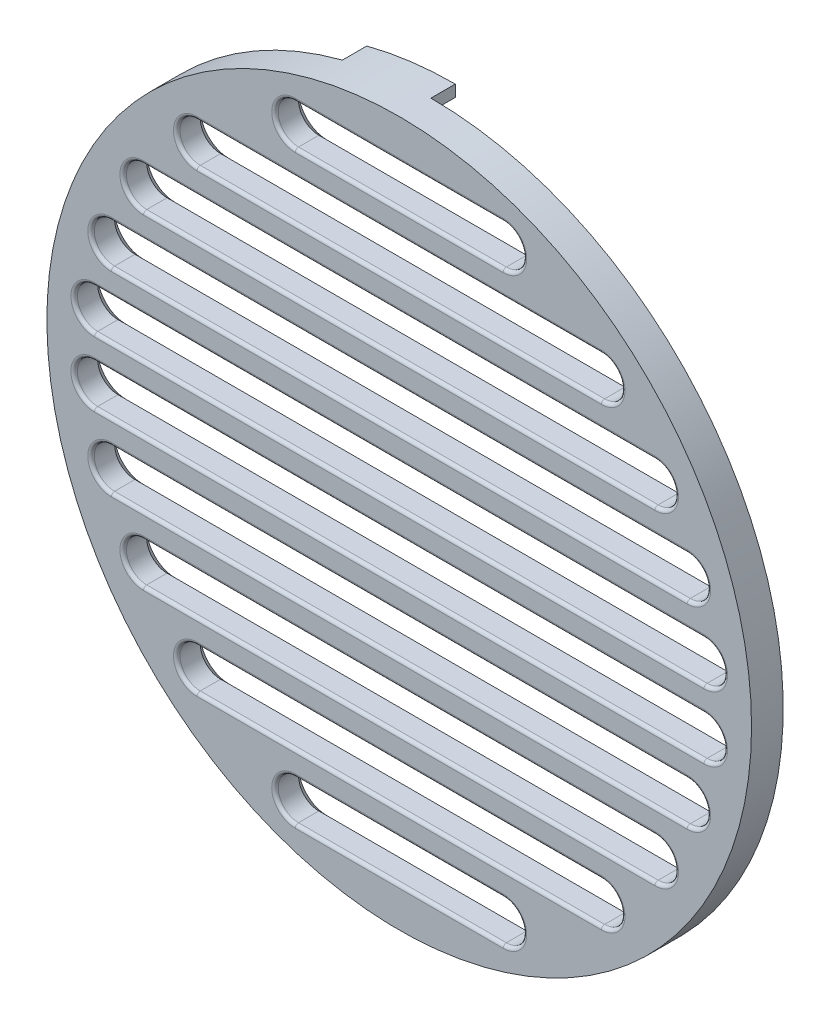
SolidWorks part; units mm, degrees
ref_plane "Alzado" through (0, 0, 0) normal (0, 0, 1) x (1, 0, 0)
ref_plane "Planta" through (0, 0, 0) normal (0, 1, 0) x (1, 0, 0)
ref_plane "Vista lateral" through (0, 0, 0) normal (1, 0, 0) x (0, 0, -1)
sketch "Croquis1" plane through (0, 0, 0) normal (0, 0, 1) x (1, 0, 0)
  line L0 (-6.3927, 18) -> (6.3927, 18) construction
  line L1 (-6.3927, 19.25) -> (6.3927, 19.25)
  line L2 (-6.3927, 16.75) -> (6.3927, 16.75)
  line L3 (0, 0) -> (0, 21) construction
  line L4 (-12.4374, 14) -> (12.4374, 14) construction
  line L5 (-12.4374, 15.25) -> (12.4374, 15.25)
  line L6 (-12.4374, 12.75) -> (12.4374, 12.75)
  line L7 (-15.7324, 10) -> (15.7324, 10) construction
  line L8 (-15.7324, 11.25) -> (15.7324, 11.25)
  line L9 (-15.7324, 8.75) -> (15.7324, 8.75)
  line L10 (-17.7088, 6) -> (17.7088, 6) construction
  line L11 (-17.7088, 7.25) -> (17.7088, 7.25)
  line L12 (-17.7088, 4.75) -> (17.7088, 4.75)
  line L13 (-18.747, 2) -> (18.747, 2) construction
  line L14 (-18.747, 3.25) -> (18.747, 3.25)
  line L15 (-18.747, 0.75) -> (18.747, 0.75)
  line L16 (12.4374, 15.25) -> (14.4374, 15.25) construction
  line L17 (6.3927, 19.25) -> (8.3927, 19.25) construction
  line L18 (15.7324, 11.25) -> (17.7324, 11.25) construction
  line L19 (17.7088, 7.25) -> (19.7088, 7.25) construction
  line L20 (18.747, 3.25) -> (20.747, 3.25) construction
  line L21 (-21, 0) -> (21, 0) construction
  line L22 (-18.747, -2) -> (18.747, -2) construction
  line L23 (-18.747, -3.25) -> (18.747, -3.25)
  line L24 (-18.747, -0.75) -> (18.747, -0.75)
  line L25 (-17.7088, -6) -> (17.7088, -6) construction
  line L26 (-17.7088, -7.25) -> (17.7088, -7.25)
  line L27 (-17.7088, -4.75) -> (17.7088, -4.75)
  line L28 (-15.7324, -10) -> (15.7324, -10) construction
  line L29 (-15.7324, -11.25) -> (15.7324, -11.25)
  line L30 (-15.7324, -8.75) -> (15.7324, -8.75)
  line L31 (-12.4374, -14) -> (12.4374, -14) construction
  line L32 (-12.4374, -15.25) -> (12.4374, -15.25)
  line L33 (-12.4374, -12.75) -> (12.4374, -12.75)
  line L34 (-6.3927, -18) -> (6.3927, -18) construction
  line L35 (-6.3927, -19.25) -> (6.3927, -19.25)
  line L36 (-6.3927, -16.75) -> (6.3927, -16.75)
  circle A0 centre (0, 0) radius 21.675
  circle A1 centre (0, 0) radius 21
  arc A2 (-6.3927, 19.25) -> (-6.3927, 16.75) centre (-6.3927, 18) ccw
  arc A3 (6.3927, 16.75) -> (6.3927, 19.25) centre (6.3927, 18) ccw
  arc A4 (-12.4374, 15.25) -> (-12.4374, 12.75) centre (-12.4374, 14) ccw
  arc A5 (12.4374, 12.75) -> (12.4374, 15.25) centre (12.4374, 14) ccw
  arc A6 (-15.7324, 11.25) -> (-15.7324, 8.75) centre (-15.7324, 10) ccw
  arc A7 (15.7324, 8.75) -> (15.7324, 11.25) centre (15.7324, 10) ccw
  arc A8 (-17.7088, 7.25) -> (-17.7088, 4.75) centre (-17.7088, 6) ccw
  arc A9 (17.7088, 4.75) -> (17.7088, 7.25) centre (17.7088, 6) ccw
  arc A10 (-18.747, 3.25) -> (-18.747, 0.75) centre (-18.747, 2) ccw
  arc A11 (18.747, 0.75) -> (18.747, 3.25) centre (18.747, 2) ccw
  arc A12 (-18.747, -3.25) -> (-18.747, -0.75) centre (-18.747, -2) cw
  arc A13 (18.747, -0.75) -> (18.747, -3.25) centre (18.747, -2) cw
  arc A14 (-17.7088, -7.25) -> (-17.7088, -4.75) centre (-17.7088, -6) cw
  arc A15 (17.7088, -4.75) -> (17.7088, -7.25) centre (17.7088, -6) cw
  arc A16 (-15.7324, -11.25) -> (-15.7324, -8.75) centre (-15.7324, -10) cw
  arc A17 (15.7324, -8.75) -> (15.7324, -11.25) centre (15.7324, -10) cw
  arc A18 (-12.4374, -15.25) -> (-12.4374, -12.75) centre (-12.4374, -14) cw
  arc A19 (12.4374, -12.75) -> (12.4374, -15.25) centre (12.4374, -14) cw
  arc A20 (-6.3927, -19.25) -> (-6.3927, -16.75) centre (-6.3927, -18) cw
  arc A21 (6.3927, -16.75) -> (6.3927, -19.25) centre (6.3927, -18) cw
  point P6 (0, 18)
  point P14 (0, 14)
  point P25 (0, 10)
  point P34 (0, 6)
  point P44 (0, 2)
  point P54 (0, -2)
  point P61 (0, -6)
  point P68 (0, -10)
  point P75 (0, -14)
  point P82 (0, -18)
  dimension "D1" = 43.35
  dimension "D2" = 42
  dimension "D3" = 2.5
  dimension "D4" = 2.5
  dimension "D5" = 2.5
  dimension "D6" = 2.5
  dimension "D7" = 2.5
  dimension "D8" = 1.5
  dimension "D9" = 1.5
  dimension "D10" = 1.5
  dimension "D11" = 1.5
  dimension "D12" = 0.75
  dimension "D13" = 2
  dimension "D14" = 2
  dimension "D15" = 2
  dimension "D16" = 2
  dimension "D17" = 2
extrude "Saliente-Extruir1" add sketch "Croquis1" along normal blind 1.95 contours A1 A11 L15 A10 L14 A9 L12 A8 L11 A7 L9 A6 L8 A5 L6 A4 L5 A3 L2 A2 L1 L24 A13 L23 A12 L27 A15 L26 A14 L30 A17 L29 A16 L33 A19 L32 A18 L36 A21 L35 A20 region at (0, 0, 0)
extrude "Saliente-Extruir2" add sketch "Croquis1<3>" along normal blind 1.95 contours A0 A1 region at (-21.0619, 0, 0)
sketch "Croquis1<3>" plane through (0, 0, 0) normal (0, 0, 1) x (1, 0, 0) same geometry as "Croquis1"
sketch "Croquis2" plane through (0, 0, 0) normal (1, 0, 0) x (0, 0, -1)
  line L0 (0, 21.675) -> (1.5, 21.675)
  line L1 (1.5, 21.675) -> (1.5, 20.9632)
  line L2 (1.5, 20.9632) -> (0, 20.9632)
  line L3 (0, -21.675) -> (0, 21.675) construction
  line L4 (0, 0) -> (-10.6328, 0) construction
  line L5 (0, 21.675) -> (0, 20.9632)
  dimension "D1" = 1.5
  dimension "D2" = 0.7118
revolve "Revolución1" add sketch "Croquis2" angle 14.55 about L4
fillet "Redondeo1" radius 0.2 40 edges at (-7.6427, -18, 1.95) (0, -19.25, 1.95) (7.6427, -18, 1.95) (0, -16.75, 1.95) (-13.6874, -14, 1.95) (0, -15.25, 1.95) (13.6874, -14, 1.95) (0, -12.75, 1.95) (-16.9824, -10, 1.95) (0, -11.25, 1.95) (16.9824, -10, 1.95) (0, -8.75, 1.95) (-18.9588, -6, 1.95) (0, -7.25, 1.95) (18.9588, -6, 1.95) (0, -4.75, 1.95) (-19.997, -2, 1.95) (0, -3.25, 1.95) (19.997, -2, 1.95) (0, -0.75, 1.95) (-19.997, 2, 1.95) (0, 0.75, 1.95) (19.997, 2, 1.95) (0, 3.25, 1.95) (-18.9588, 6, 1.95) (18.9588, 6, 1.95) (0, 7.25, 1.95) (0, 4.75, 1.95) (-16.9824, 10, 1.95) (0, 8.75, 1.95) (16.9824, 10, 1.95) (0, 11.25, 1.95) (-13.6874, 14, 1.95) (0, 12.75, 1.95) (13.6874, 14, 1.95) (0, 15.25, 1.95) (0, 19.25, 1.95) (7.6427, 18, 1.95) (-7.6427, 18, 1.95) (0, 16.75, 1.95)
chamfer "Chaflán1" distance 0.5 angle 45 4 edges at (-7.6427, 18, 0) (0, 16.75, 0) (7.6427, 18, 0) (0, 19.25, 0)
chamfer "Chaflán2" distance 0.5 angle 45 36 edges at (-16.9824, 10, 0) (0, 8.75, 0) (16.9824, 10, 0) (0, 11.25, 0) (-13.6874, 14, 0) (0, 12.75, 0) (13.6874, 14, 0) (0, 15.25, 0) (-7.6427, -18, 0) (0, -19.25, 0) (7.6427, -18, 0) (0, -16.75, 0) (-13.6874, -14, 0) (0, -15.25, 0) (13.6874, -14, 0) (0, -12.75, 0) (-16.9824, -10, 0) (0, -11.25, 0) (16.9824, -10, 0) (0, -8.75, 0) (-18.9588, -6, 0) (0, -7.25, 0) (18.9588, -6, 0) (0, -4.75, 0) (-19.997, -2, 0) (0, -3.25, 0) (19.997, -2, 0) (0, -0.75, 0) (0, 3.25, 0) (19.997, 2, 0) (0, 0.75, 0) (-19.997, 2, 0) (0, 4.75, 0) (-18.9588, 6, 0) (18.9588, 6, 0) (0, 7.25, 0) tangent propagation no
